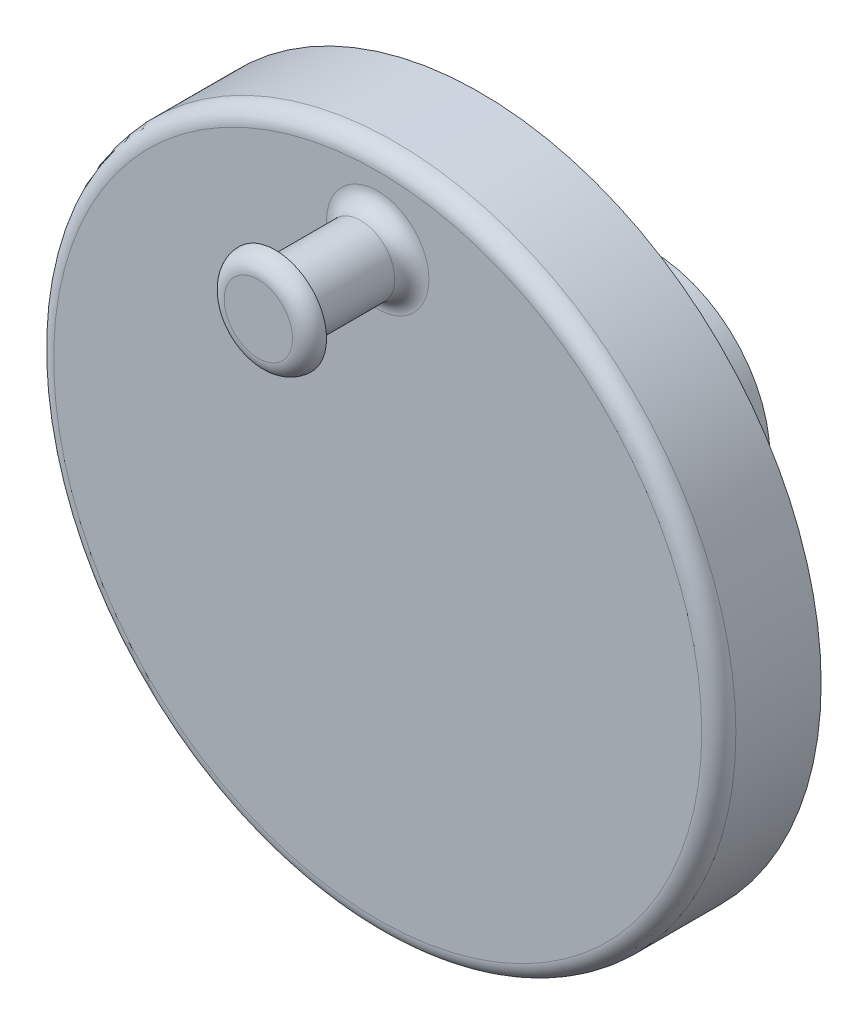
SolidWorks part; units mm, degrees
ref_plane "Front Plane" through (0, 0, 0) normal (0, 0, 1) x (1, 0, 0)
ref_plane "Top Plane" through (0, 0, 0) normal (0, 1, 0) x (1, 0, 0)
ref_plane "Right Plane" through (0, 0, 0) normal (1, 0, 0) x (0, 0, -1)
sketch "Sketch1" plane through (0, 0, 0) normal (0, 0, 1) x (1, 0, 0)
  circle A0 centre (0, 0) radius 20
  dimension "D1" = 40
extrude "Boss-Extrude1" add sketch "Sketch1" along normal blind 6
sketch "Sketch2" plane through (0, 0, 0) normal (0, 0, -1) x (-1, 0, 0)
  circle A0 centre (0, 0) radius 3
  circle A1 centre (0, 0) radius 7
  dimension "D1" = 6
  dimension "D2" = 4
extrude "Boss-Extrude2" add sketch "Sketch2" along normal blind 10
sketch "Sketch3" plane through (0, 0, 6) normal (0, 0, 1) x (1, 0, 0)
  circle A0 centre (0, 15) radius 2
  dimension "D1" = 4
  dimension "D2" = 15
extrude "Boss-Extrude3" add sketch "Sketch3" along normal blind 7
sketch "Sketch4" plane through (0, 0, 13) normal (0, 0, 1) x (1, 0, 0)
  circle A0 centre (0, 15) radius 3
  dimension "D1" = 6
extrude "Boss-Extrude4" add sketch "Sketch4" against normal blind 1
fillet "Fillet1" radius 1 4 edges at (20, 0, 6) (2, 15, 6) (3, 15, 13) (7, 0, 0)
